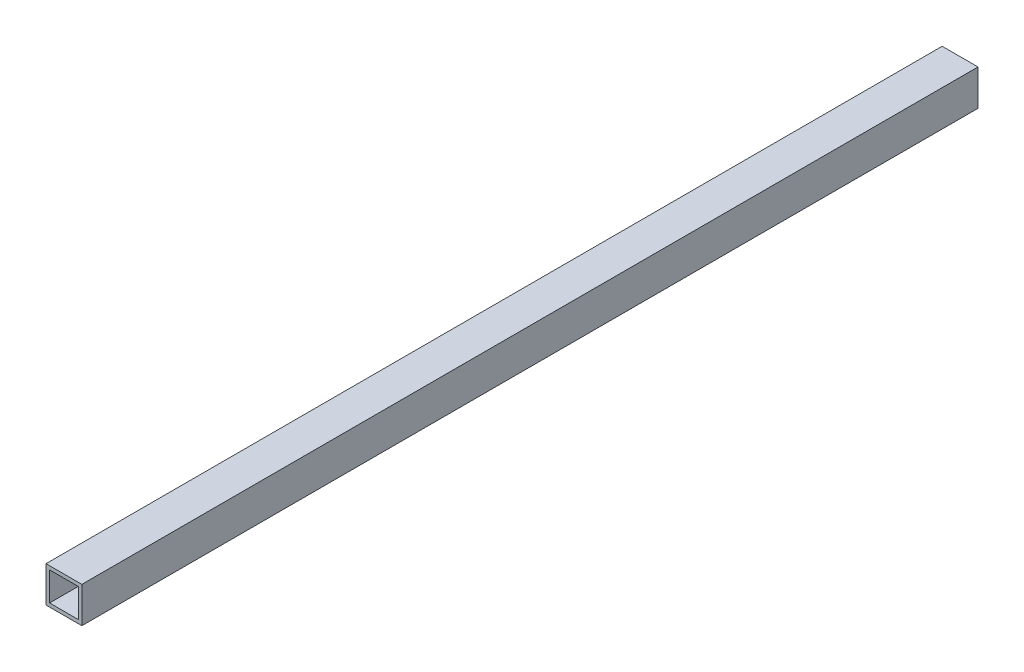
SolidWorks part; units mm, degrees
material "Thornel Mat VMA"
ref_plane "前视基准面" through (0, 0, 0) normal (0, 0, 1) x (1, 0, 0)
ref_plane "上视基准面" through (0, 0, 0) normal (0, 1, 0) x (1, 0, 0)
ref_plane "右视基准面" through (0, 0, 0) normal (1, 0, 0) x (0, 0, -1)
sketch "草图1" plane through (0, 0, 0) normal (0, 0, 1) x (1, 0, 0)
  line L1 (5, 5) -> (-5, 5)
  line L2 (5, 5) -> (5, -5)
  line L3 (5, -5) -> (-5, -5)
  line L4 (-5, 5) -> (-5, -5)
  line L5 (5, 5) -> (-5, -5) construction
  line L6 (5, -5) -> (-5, 5) construction
  line L7 (4, 4) -> (-4, 4)
  line L8 (4, 4) -> (4, -4)
  line L9 (4, -4) -> (-4, -4)
  line L10 (-4, 4) -> (-4, -4)
  line L11 (4, 4) -> (-4, -4) construction
  line L12 (4, -4) -> (-4, 4) construction
  point P0 (0, 0)
  point P6 (0, 0)
  dimension "D1" = 10
  dimension "D2" = 1
extrude "凸台-拉伸1" add sketch "草图1" along normal blind 250
